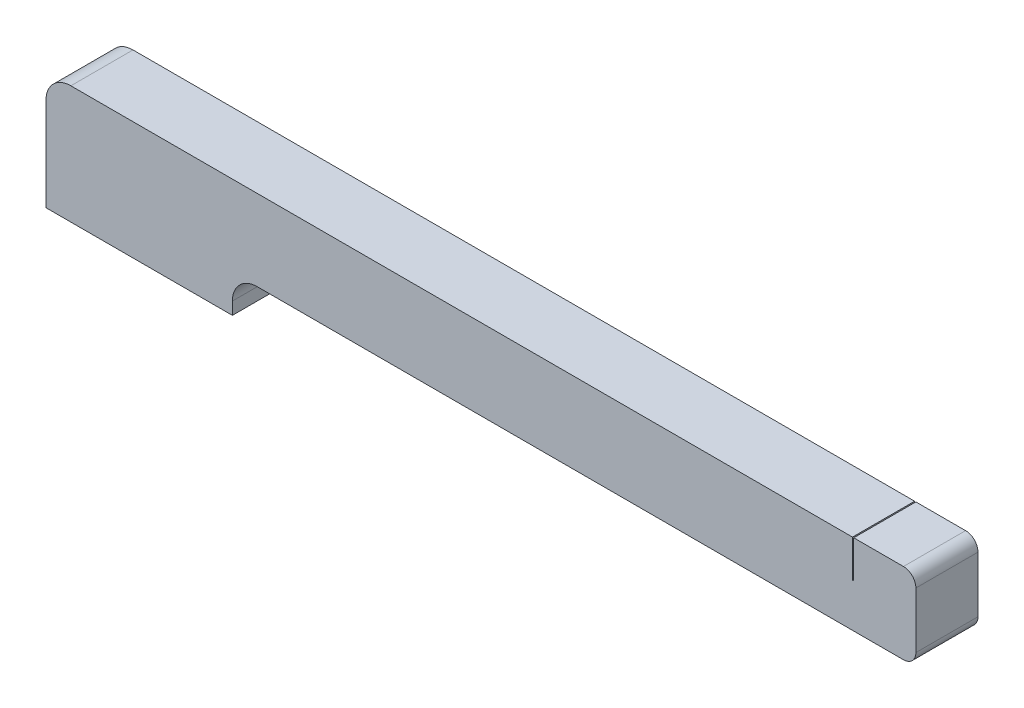
SolidWorks part; units mm, degrees
ref_plane "Front Plane" through (0, 0, 0) normal (0, 0, 1) x (1, 0, 0)
ref_plane "Top Plane" through (0, 0, 0) normal (0, 1, 0) x (1, 0, 0)
ref_plane "Right Plane" through (0, 0, 0) normal (1, 0, 0) x (0, 0, -1)
sketch "Sketch1" plane through (0, 0, 0) normal (0, 0, 1) x (1, 0, 0)
  line L0 (0, 0) -> (0, 7.5)
  line L1 (2, 9.5) -> (69, 9.5)
  line L2 (70, 8.5) -> (70, 4)
  line L3 (69, 3) -> (17, 3)
  line L4 (15, 1) -> (15, 0)
  line L5 (15, 0) -> (0, 0)
  arc A0 (17, 3) -> (15, 1) centre (17, 1) ccw
  arc A1 (2, 9.5) -> (0, 7.5) centre (2, 7.5) ccw
  arc A2 (70, 8.5) -> (69, 9.5) centre (69, 8.5) ccw
  arc A3 (69, 3) -> (70, 4) centre (69, 4) ccw
  point P11 (0, 9.5)
  point P14 (70, 9.5)
  point P17 (70, 3)
  dimension "D5" = 2
  dimension "D6" = 2
  dimension "D7" = 1
  dimension "D2" = 15
  dimension "D3" = 6.5
  dimension "D4" = 70
extrude "Boss-Extrude1" add sketch "Sketch1" along normal blind 5
sketch "Sketch3" plane through (0, 9.5, 0) normal (0, 1, 0) x (1, 0, 0)
  line L0 (0, -2.5) -> (64.95, -2.5) construction
  line L1 (0, -5) -> (0, 0) construction
  line L2 (69, 0) -> (2, 0) construction
  line L3 (64.9, -5) -> (65, -5)
  line L4 (64.9, -5) -> (64.9, 0)
  line L5 (64.9, 0) -> (65, 0)
  line L6 (65, -5) -> (65, 0)
  line L7 (64.9, -5) -> (65, 0) construction
  line L8 (64.9, 0) -> (65, -5) construction
  dimension "D1" = 64.95
extrude "Cut-Extrude1" cut sketch "Sketch3" against normal blind 3
equation "\"A.L\"= 0.07m"
equation "\"A.h\"= 0.007m"
equation "\"A.d\"= 0.005m"
equation "\"A.delta\"= 45.0001"
equation "\"A.w\"= 0m"
equation "\"A.v\"= 0.013m"
equation "\"A.s\"= 0.014m"
equation "\"A.t\"= 0.007m"
equation "\"B.L\"= 0.065m"
equation "\"B.h\"= 0.008m"
equation "\"B.s\"= 0.016m"
equation "\"B.t\"= 0.008m"
equation "\"C.h\"= 0.0065m"
equation "\"C.d\"= 0.005m"
equation "\"C.L\"= 0.05m"
equation "\"C.wmax\"= 0.003m"
equation "\"D.L\"= 0.06m"
equation "\"D.h\"= 0.008m"
equation "\"D.s\"= 0.012m"
equation "\"D.t\"= 0.008m"
equation "\"a_h\"= 0.0001m"
equation "\"a_d\"= 0.005m"
equation "\"a_L\"= 0.008m"
equation "\"b_h\"= 0.0004m"
equation "\"b_d\"= 0.005m"
equation "\"b_L\"= 0.007m"
equation "\"c_h\"= 0.0001m"
equation "\"c_d\"= 0.005m"
equation "\"c_L\"= 0.01m"
equation "\"d_h\"= 0.0001m"
equation "\"d_d\"= 0.005m"
equation "\"d_L\"= 0.01m"
equation "\"S.h\"= 0.015m"
equation "\"S.L\"= 0.09275m"
equation "\"D1@Sketch1\"=\"C.h\"+\"C.wmax\""
equation "\"D2@Sketch1\"=\"S.h\""
equation "\"D3@Sketch1\"=\"C.h\""
equation "\"D4@Sketch1\"=\"C.L\"+\"S.h\"+0.005"
equation "\"D1@Boss-Extrude1\"=0.005m"
equation "\"D1@Sketch3\"=\"C.L\"+\"S.h\"-\"c_h\"/2"
equation "\"D2@Sketch3\"=\"c_h\""
